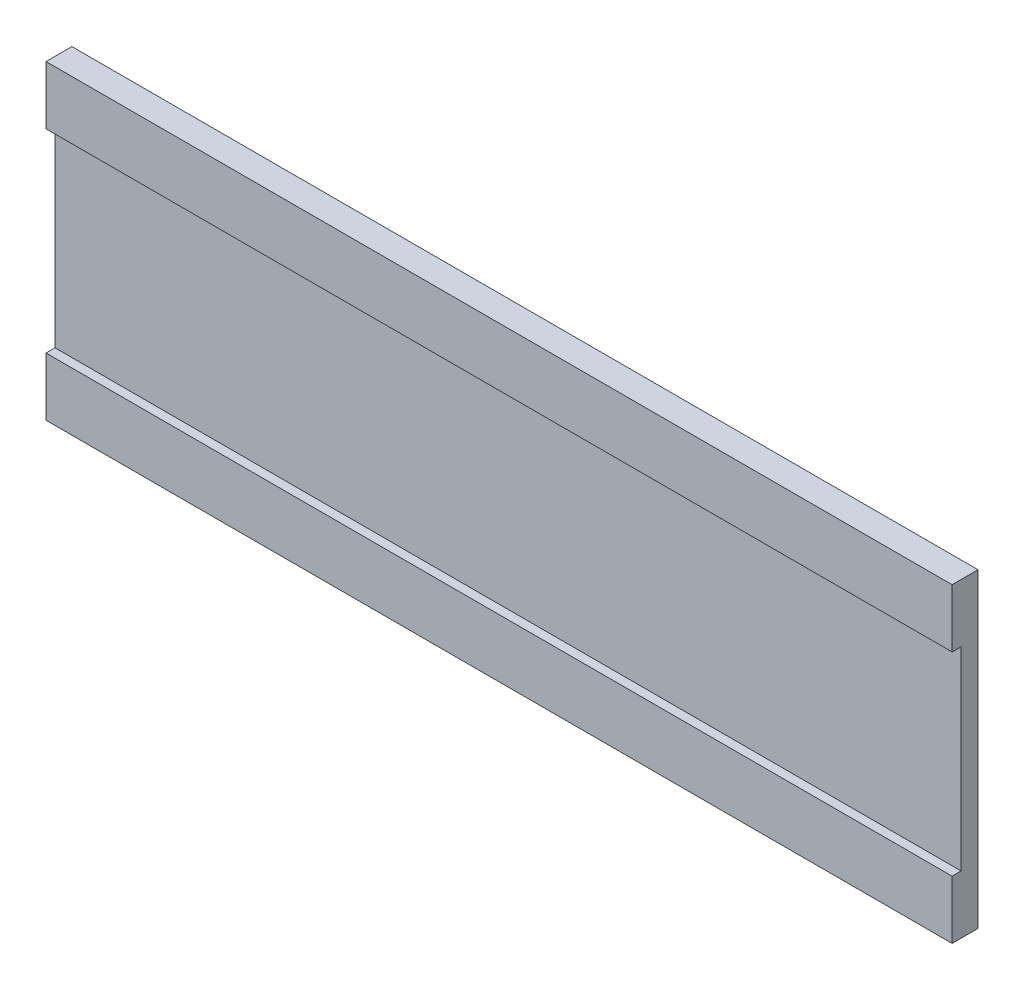
SolidWorks part; units mm, degrees
ref_plane "Plan de face" through (0, 0, 0) normal (0, 0, 1) x (1, 0, 0)
ref_plane "Plan de dessus" through (0, 0, 0) normal (0, 1, 0) x (1, 0, 0)
ref_plane "Plan de droite" through (0, 0, 0) normal (1, 0, 0) x (0, 0, -1)
sketch "Esquisse1" plane through (0, 0, 0) normal (0, 0, 1) x (1, 0, 0)
  line L1 (-33.559, 25.9394) -> (106.441, 25.9394)
  line L2 (-33.559, 25.9394) -> (-33.559, -22.0606)
  line L3 (-33.559, -22.0606) -> (106.441, -22.0606)
  line L4 (106.441, 25.9394) -> (106.441, -22.0606)
  dimension "D1" = 48
  dimension "D2" = 140
extrude "Boss.-Extru.1" add sketch "Esquisse1" along normal blind 4
sketch "Esquisse2" plane through (-33.559, 0, 0) normal (-1, 0, 0) x (0, 0, 1)
  line L0 (4, 25.9394) -> (4, -22.0606) construction
  line L1 (4, 16.9394) -> (2.6099, 16.9394)
  line L2 (4, 16.9394) -> (4, -13.0606)
  line L3 (4, -13.0606) -> (2.6099, -13.0606)
  line L4 (2.6099, 16.9394) -> (2.6099, -13.0606)
  line L5 (4, 25.9394) -> (0, 25.9394) construction
  line L6 (4, -22.0606) -> (0, -22.0606) construction
  dimension "D1" = 9
  dimension "D2" = 9
extrude "Enlèv. mat.-Extru.1" cut sketch "Esquisse2" against normal through all
sketch "Esquisse3" plane through (0, 0, 2.6099) normal (0, 0, 1) x (1, 0, 0)
  line L0 (106.441, 25.9394) -> (-33.559, 25.9394) construction
  circle A0 centre (-10.6412, 19.9394) radius 1.5
  circle A1 centre (-10.6412, -15.0606) radius 1.5
  circle A2 centre (89.3588, -15.0606) radius 1.5
  circle A3 centre (89.3588, 19.9394) radius 1.5
  dimension "D1" = 3
  dimension "D2" = 3
  dimension "D3" = 3
  dimension "D4" = 3
  dimension "D5" = 6
  dimension "D6" = 35
  dimension "D7" = 6
  dimension "D8" = 35
  dimension "D9" = 100
  dimension "D10" = 100
